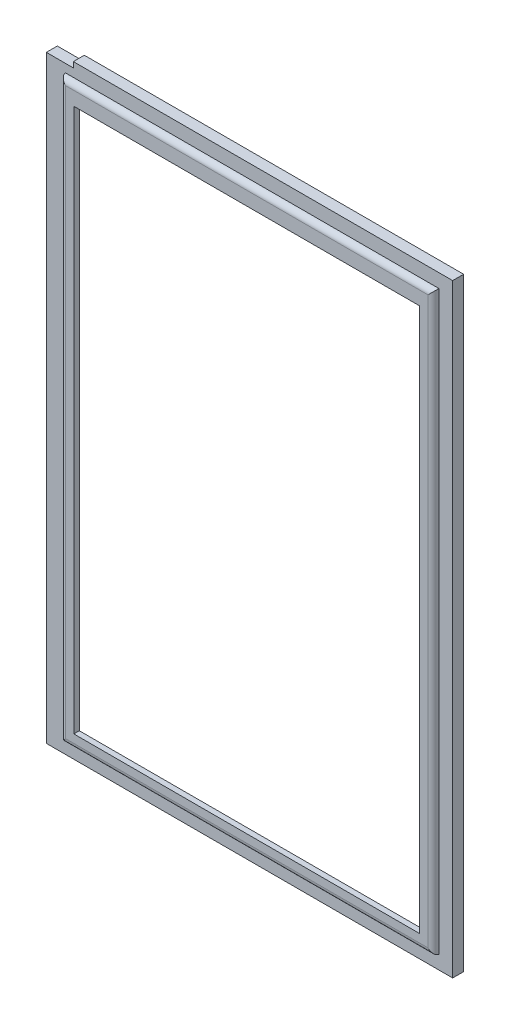
SolidWorks part; units mm, degrees
material "Borracha"
ref_plane "Plano frontal" through (0, 0, 0) normal (0, 0, 1) x (1, 0, 0)
ref_plane "Plano superior" through (0, 0, 0) normal (0, 1, 0) x (1, 0, 0)
ref_plane "Plano direito" through (0, 0, 0) normal (1, 0, 0) x (0, 0, -1)
other "plano sup"
sketch "Esboço2" plane through (0, 0, 0) normal (0, 0, 1) x (1, 0, 0)
  line L0 (0, 0) -> (740, 0)
  line L12 (0, 0) -> (0, -1100)
  line L13 (0, -1100) -> (740, -1100)
  line L14 (740, -1100) -> (740, 0)
  line L23 (35, -25) -> (715, -25)
  line L24 (35, -25) -> (35, -1075)
  line L25 (35, -1075) -> (715, -1075)
  line L26 (715, -25) -> (715, -1075)
  dimension "D3" = 35
  dimension "D1" = 740
  dimension "D2" = 1100
  dimension "D4" = 25
  dimension "D5" = 25
  dimension "D6" = 25
extrude "Ressalto-extrusão1" add sketch "Esboço2" along normal blind 20
ref_plane "Plano1" through (0, 0, 20) normal (0, 0, 1) x (1, 0, 0)
sketch "Esboço3" plane through (0, 0, 20) normal (0, 0, 1) x (1, 0, 0)
  line L1 (35, -25) -> (715, -25)
  line L2 (35, -25) -> (35, -1075)
  line L3 (35, -1075) -> (715, -1075)
  line L4 (715, -25) -> (715, -1075)
  line L5 (60, -1050) -> (690, -1050)
  line L6 (60, -1050) -> (60, -60)
  line L7 (60, -60) -> (690, -60)
  line L8 (690, -1050) -> (690, -60)
  dimension "D1" = 35
  dimension "D2" = 25
  dimension "D3" = 25
  dimension "D4" = 25
extrude "Ressalto-extrusão2" add sketch "Esboço3" along normal blind 10 separate body
fillet "Filete1" radius 10 4 edges at (35, -550, 30) (375, -1075, 30) (715, -550, 30) (375, -25, 30) type face fillet first side face at (375, -550, 30) second side face at (375, -1075, 25) second side face at (35, -550, 25) second side face at (375, -25, 25) second side face at (715, -550, 25)
sketch "Esboço4" plane through (0, 0, 20) normal (0, 0, 1) x (1, 0, 0)
  line L1 (0, 0) -> (49.1432, 0)
  line L2 (0, 0) -> (0, -10)
  line L3 (0, -10) -> (49.1432, -10)
  line L4 (49.1432, 0) -> (49.1432, -10)
  dimension "D1" = 49.1432
  dimension "D2" = 10
extrude "Corte-extrusão1" cut sketch "Esboço4" against normal up to next (20 mm away)
